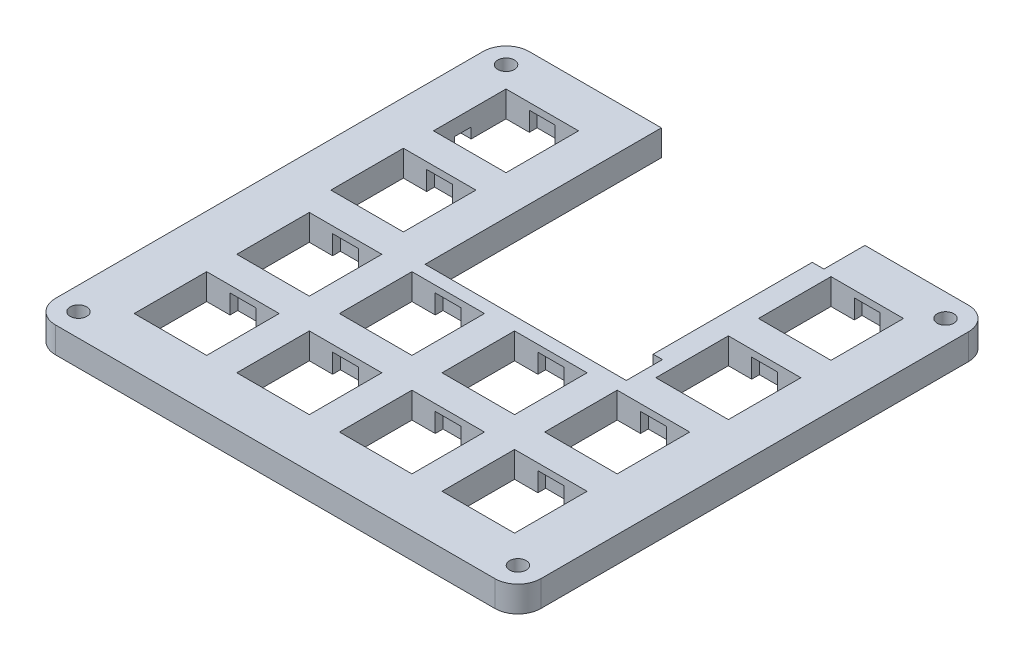
SolidWorks part; units mm, degrees
ref_plane "Front Plane" through (0, 0, 0) normal (0, 0, 1) x (1, 0, 0)
ref_plane "Top Plane" through (0, 0, 0) normal (0, 1, 0) x (1, 0, 0)
ref_plane "Right Plane" through (0, 0, 0) normal (1, 0, 0) x (0, 0, -1)
sketch "Sketch2" plane through (0, 0, 0) normal (0, 1, 0) x (1, 0, 0)
  line L6 (-46.8585, -41.275) -> (-46.8585, 41.275)
  line L8 (46.8585, -41.275) -> (46.8585, 41.275)
  line L9 (42.418, -45.7155) -> (-42.418, -45.7155)
  line L10 (-42.418, 45.7155) -> (-16.8754, 45.7155)
  line L12 (22.418, 41.275) -> (22.418, 39.575)
  line L13 (22.418, 39.575) -> (22.418, 37.7973)
  line L16 (42.418, 27.292) -> (38.3626, 27.292)
  line L18 (42.418, 30.492) -> (38.3626, 30.492)
  line L19 (42.418, 30.492) -> (46.218, 30.492)
  line L20 (46.218, 30.492) -> (46.218, 27.292)
  line L21 (46.218, 27.292) -> (42.418, 27.292)
  line L24 (-46.218, 28.892) -> (-46.218, 30.492)
  line L25 (-46.218, 30.492) -> (-38.3754, 30.492)
  line L26 (-46.218, 28.892) -> (-46.218, 27.292)
  line L27 (-46.218, 27.292) -> (-38.3754, 27.292)
  line L29 (20.1687, 37.7973) -> (20.1687, 9.575)
  line L30 (22.418, 37.7973) -> (20.1687, 37.7973)
  line L31 (20.1687, 9.575) -> (20.1687, 7.075)
  line L32 (20.1687, 7.075) -> (21.9687, 7.075)
  line L33 (-9.9124, 0.0949) -> (21.9687, 0.0949)
  line L35 (21.9687, 7.075) -> (21.9687, 0.0949)
  line L36 (22.418, 41.275) -> (22.418, 45.7155)
  line L38 (-16.8754, 30.2189) -> (-16.8754, 0.0949)
  line L39 (-16.8754, 0.0949) -> (-9.9124, 0.0949)
  line L40 (-16.8754, 30.2189) -> (-16.8754, 45.7155)
  line L41 (-31.3754, 37.2189) -> (-38.3754, 37.2189)
  line L42 (-38.3754, 37.2189) -> (-38.3754, 23.2189)
  line L43 (-38.3754, 23.2189) -> (-24.3754, 23.2189)
  line L44 (-24.3754, 23.2189) -> (-24.3754, 37.2189)
  line L45 (-24.3754, 37.2189) -> (-31.3754, 37.2189)
  line L47 (-38.3754, 10.4069) -> (-38.3754, 17.4069)
  line L48 (-38.3754, 17.4069) -> (-24.3754, 17.4069)
  line L49 (-24.3754, 17.4069) -> (-24.3754, 3.4069)
  line L50 (-24.3754, 3.4069) -> (-38.3754, 3.4069)
  line L51 (-38.3754, 3.4069) -> (-38.3754, 10.4069)
  line L53 (-36.7244, -9.4051) -> (-36.7244, -2.4051)
  line L54 (-36.7244, -2.4051) -> (-22.7244, -2.4051)
  line L55 (-22.7244, -2.4051) -> (-22.7244, -16.4051)
  line L56 (-22.7244, -16.4051) -> (-36.7244, -16.4051)
  line L57 (-36.7244, -16.4051) -> (-36.7244, -9.4051)
  line L59 (-36.7244, -29.2171) -> (-36.7244, -22.2171)
  line L60 (-36.7244, -22.2171) -> (-22.7244, -22.2171)
  line L61 (-22.7244, -22.2171) -> (-22.7244, -36.2171)
  line L62 (-22.7244, -36.2171) -> (-36.7244, -36.2171)
  line L63 (-36.7244, -36.2171) -> (-36.7244, -29.2171)
  line L65 (-9.9124, -22.2171) -> (-2.9124, -22.2171)
  line L66 (-2.9124, -22.2171) -> (-2.9124, -36.2171)
  line L67 (-2.9124, -36.2171) -> (-16.9124, -36.2171)
  line L68 (-16.9124, -36.2171) -> (-16.9124, -22.2171)
  line L69 (-16.9124, -22.2171) -> (-9.9124, -22.2171)
  line L71 (-9.9124, -16.4051) -> (-2.9124, -16.4051)
  line L72 (-2.9124, -16.4051) -> (-2.9124, -2.4051)
  line L73 (-2.9124, -2.4051) -> (-16.9124, -2.4051)
  line L74 (-16.9124, -2.4051) -> (-16.9124, -16.4051)
  line L75 (-16.9124, -16.4051) -> (-9.9124, -16.4051)
  line L77 (9.8996, -2.4051) -> (2.8996, -2.4051)
  line L78 (2.8996, -2.4051) -> (2.8996, -16.4051)
  line L79 (2.8996, -16.4051) -> (16.8996, -16.4051)
  line L80 (16.8996, -16.4051) -> (16.8996, -2.4051)
  line L81 (16.8996, -2.4051) -> (9.8996, -2.4051)
  line L83 (9.8996, -22.2171) -> (2.8996, -22.2171)
  line L84 (2.8996, -22.2171) -> (2.8996, -36.2171)
  line L85 (2.8996, -36.2171) -> (16.8996, -36.2171)
  line L86 (16.8996, -36.2171) -> (16.8996, -22.2171)
  line L87 (16.8996, -22.2171) -> (9.8996, -22.2171)
  line L89 (36.7116, -29.2171) -> (36.7116, -22.2171)
  line L90 (36.7116, -22.2171) -> (22.7116, -22.2171)
  line L91 (22.7116, -22.2171) -> (22.7116, -36.2171)
  line L92 (22.7116, -36.2171) -> (36.7116, -36.2171)
  line L93 (36.7116, -36.2171) -> (36.7116, -29.2171)
  line L95 (29.7116, -2.4051) -> (22.7116, -2.4051)
  line L96 (22.7116, -2.4051) -> (22.7116, -16.4051)
  line L97 (22.7116, -16.4051) -> (36.7116, -16.4051)
  line L98 (36.7116, -16.4051) -> (36.7116, -2.4051)
  line L99 (36.7116, -2.4051) -> (29.7116, -2.4051)
  line L101 (38.3626, 10.4069) -> (38.3626, 17.4069)
  line L102 (38.3626, 17.4069) -> (24.3626, 17.4069)
  line L103 (24.3626, 17.4069) -> (24.3626, 3.4069)
  line L104 (24.3626, 3.4069) -> (38.3626, 3.4069)
  line L105 (38.3626, 3.4069) -> (38.3626, 10.4069)
  line L106 (38.3626, 30.2189) -> (38.3626, 23.2189)
  line L107 (38.3626, 23.2189) -> (24.3626, 23.2189)
  line L108 (24.3626, 23.2189) -> (24.3626, 37.2189)
  line L109 (24.3626, 37.2189) -> (38.3626, 37.2189)
  line L110 (38.3626, 37.2189) -> (38.3626, 30.2189)
  line L111 (22.418, 45.7155) -> (42.418, 45.7155)
  arc A0 (-42.418, 45.7155) -> (-46.8585, 41.275) centre (-42.418, 41.275) ccw
  arc A1 (42.418, 45.7155) -> (46.8585, 41.275) centre (42.418, 41.275) cw
  arc A2 (-46.8585, -41.275) -> (-42.418, -45.7155) centre (-42.418, -41.275) ccw
  arc A3 (46.8585, -41.275) -> (42.418, -45.7155) centre (42.418, -41.275) cw
  circle A4 centre (42.418, 41.275) radius 1.6
  circle A5 centre (-42.418, 41.275) radius 1.6
  circle A6 centre (-42.418, -41.275) radius 1.6
  circle A7 centre (42.418, -41.275) radius 1.6
extrude "Boss-Extrude1" add sketch "Sketch2" along normal blind 5 contours A3 L8 A1 L111 L36 L12 L13 L30 L29 L31 L32 L35 L33 L39 L38 L40 L10 A0 L6 A2 L9 A7 A6 A5 A4 L105 L104 L103 L102 L101 L99 L98 L97 L96 L95 L93 L92 L91 L90 L89 L87 L86 L85 | L42 L25 L24 L26 L27 | L18 L110 L106 L16 L21 L20 L19 region at (-0.7763, 0, 6.0484) region at (42.2903, 0, -28.892) region at (-42.2967, 0, -28.892)
sketch "Sketch3" plane through (0, 0, 0) normal (0, -1, 0) x (1, 0, 0)
  line L0 (42.418, -41.275) -> (42.418, -28.892)
  line L1 (42.418, -28.892) -> (46.218, -28.892)
  line L2 (46.218, -28.892) -> (46.218, -27.292)
  line L3 (46.218, -27.292) -> (38.3626, -27.292)
  line L4 (38.3626, -37.2189) -> (38.3626, -23.2189) construction
  line L5 (46.218, -28.892) -> (46.218, -30.492)
  line L6 (46.218, -30.492) -> (38.3626, -30.492)
  line L7 (38.3626, -30.492) -> (38.3626, -27.292)
  line L8 (-42.418, -41.275) -> (-42.418, -28.892)
  line L9 (-42.418, -28.892) -> (-46.218, -28.892)
  line L10 (-46.218, -28.892) -> (-46.218, -30.492)
  line L11 (-46.218, -28.892) -> (-46.218, -27.292)
  line L12 (-46.218, -27.292) -> (-38.3754, -27.292)
  line L13 (-38.3754, -37.2189) -> (-38.3754, -23.2189) construction
  line L14 (-46.218, -30.492) -> (-38.3754, -30.492)
  line L15 (-38.3754, -30.492) -> (-38.3754, -27.292)
extrude "Cut-Extrude1" cut sketch "Sketch3" against normal blind 2 contours L7 L6 L0 L1 L2 L3 | L6 L5 L1 L0 | L14 L15 L12 L11 L9 L8 | L10 L14 L8 L9 region at (41.6434, 0, -28.6368) region at (44.318, 0, -29.692) region at (-44.318, 0, -29.692) region at (-41.6504, 0, -28.6362)
sketch "Sketch4" plane through (0, 0, 0) normal (0, -1, 0) x (1, 0, 0)
  line L0 (31.3626, -37.2189) -> (31.3626, -38.7189)
  line L1 (24.3626, -37.2189) -> (38.3626, -37.2189) construction
  line L2 (31.3626, -38.7189) -> (28.8626, -38.7189)
  line L3 (28.8626, -38.7189) -> (28.8626, -37.2189)
  line L4 (28.8626, -37.2189) -> (33.8626, -37.2189)
  line L5 (33.8626, -37.2189) -> (33.8626, -38.7189)
  line L6 (33.8626, -38.7189) -> (31.3626, -38.7189)
  line L7 (31.3626, -23.2189) -> (31.3626, -21.7189)
  line L8 (38.3626, -23.2189) -> (24.3626, -23.2189) construction
  line L9 (31.3626, -21.7189) -> (33.8626, -21.7189)
  line L10 (33.8626, -21.7189) -> (33.8626, -23.2189)
  line L11 (33.8626, -23.2189) -> (28.8626, -23.2189)
  line L12 (28.8626, -23.2189) -> (28.8626, -21.7189)
  line L13 (28.8626, -21.7189) -> (31.3626, -21.7189)
  line L14 (31.3626, -17.4069) -> (31.3626, -18.9069)
  line L15 (38.3626, -17.4069) -> (24.3626, -17.4069) construction
  line L16 (31.3626, -18.9069) -> (33.8626, -18.9069)
  line L17 (33.8626, -18.9069) -> (33.8626, -17.4069)
  line L18 (33.8626, -17.4069) -> (28.8626, -17.4069)
  line L19 (28.8626, -17.4069) -> (28.8626, -18.9069)
  line L20 (28.8626, -18.9069) -> (31.3626, -18.9069)
  line L21 (31.3626, -3.4069) -> (31.3626, -1.9069)
  line L22 (24.3626, -3.4069) -> (38.3626, -3.4069) construction
  line L23 (31.3626, -1.9069) -> (33.8626, -1.9069)
  line L24 (33.8626, -1.9069) -> (33.8626, -3.4069)
  line L25 (33.8626, -3.4069) -> (28.8626, -3.4069)
  line L26 (28.8626, -3.4069) -> (28.8626, -1.9069)
  line L27 (28.8626, -1.9069) -> (31.3626, -1.9069)
  line L28 (29.7116, 2.4051) -> (29.7116, 0.9051)
  line L29 (36.7116, 2.4051) -> (22.7116, 2.4051) construction
  line L30 (29.7116, 0.9051) -> (32.2116, 0.9051)
  line L31 (32.2116, 0.9051) -> (32.2116, 2.4051)
  line L32 (32.2116, 2.4051) -> (27.2116, 2.4051)
  line L33 (27.2116, 2.4051) -> (27.2116, 0.9051)
  line L34 (27.2116, 0.9051) -> (29.7116, 0.9051)
  line L35 (29.7116, 16.4051) -> (29.7116, 17.9051)
  line L36 (22.7116, 16.4051) -> (36.7116, 16.4051) construction
  line L37 (29.7116, 17.9051) -> (32.2116, 17.9051)
  line L38 (32.2116, 17.9051) -> (32.2116, 16.4051)
  line L39 (32.2116, 16.4051) -> (27.2116, 16.4051)
  line L40 (27.2116, 16.4051) -> (27.2116, 17.9051)
  line L41 (27.2116, 17.9051) -> (29.7116, 17.9051)
  line L42 (29.7116, 22.2171) -> (29.7116, 20.7171)
  line L43 (36.7116, 22.2171) -> (22.7116, 22.2171) construction
  line L44 (29.7116, 20.7171) -> (32.2116, 20.7171)
  line L45 (32.2116, 20.7171) -> (32.2116, 22.2171)
  line L46 (32.2116, 22.2171) -> (27.2116, 22.2171)
  line L47 (27.2116, 22.2171) -> (27.2116, 20.7171)
  line L48 (27.2116, 20.7171) -> (29.7116, 20.7171)
  line L49 (29.7116, 36.2171) -> (29.7116, 37.7171)
  line L50 (22.7116, 36.2171) -> (36.7116, 36.2171) construction
  line L51 (29.7116, 37.7171) -> (32.2116, 37.7171)
  line L52 (32.2116, 37.7171) -> (32.2116, 36.2171)
  line L53 (32.2116, 36.2171) -> (27.2116, 36.2171)
  line L54 (27.2116, 36.2171) -> (27.2116, 37.7171)
  line L55 (27.2116, 37.7171) -> (29.7116, 37.7171)
  line L56 (9.8996, 2.4051) -> (9.8996, 0.9051)
  line L57 (16.8996, 2.4051) -> (2.8996, 2.4051) construction
  line L58 (9.8996, 0.9051) -> (12.3996, 0.9051)
  line L59 (12.3996, 0.9051) -> (12.3996, 2.4051)
  line L60 (12.3996, 2.4051) -> (7.3996, 2.4051)
  line L61 (7.3996, 2.4051) -> (7.3996, 0.9051)
  line L62 (7.3996, 0.9051) -> (9.8996, 0.9051)
  line L63 (9.8996, 16.4051) -> (9.8996, 17.9051)
  line L64 (2.8996, 16.4051) -> (16.8996, 16.4051) construction
  line L65 (9.8996, 17.9051) -> (7.3996, 17.9051)
  line L66 (7.3996, 17.9051) -> (7.3996, 16.4051)
  line L67 (7.3996, 16.4051) -> (12.3996, 16.4051)
  line L68 (12.3996, 16.4051) -> (12.3996, 17.9051)
  line L69 (12.3996, 17.9051) -> (9.8996, 17.9051)
  line L70 (9.8996, 22.2171) -> (9.8996, 20.7171)
  line L71 (16.8996, 22.2171) -> (2.8996, 22.2171) construction
  line L72 (9.8996, 20.7171) -> (7.3996, 20.7171)
  line L73 (7.3996, 20.7171) -> (7.3996, 22.2171)
  line L74 (7.3996, 22.2171) -> (12.3996, 22.2171)
  line L75 (12.3996, 22.2171) -> (12.3996, 20.7171)
  line L76 (12.3996, 20.7171) -> (9.8996, 20.7171)
  line L77 (9.8996, 36.2171) -> (9.8996, 37.7171)
  line L78 (2.8996, 36.2171) -> (16.8996, 36.2171) construction
  line L79 (9.8996, 37.7171) -> (7.3996, 37.7171)
  line L80 (7.3996, 37.7171) -> (7.3996, 36.2171)
  line L81 (7.3996, 36.2171) -> (12.3996, 36.2171)
  line L82 (12.3996, 36.2171) -> (12.3996, 37.7171)
  line L83 (12.3996, 37.7171) -> (9.8996, 37.7171)
  line L84 (-9.9124, 2.4051) -> (-9.9124, 0.9051)
  line L85 (-2.9124, 2.4051) -> (-16.9124, 2.4051) construction
  line L86 (-9.9124, 0.9051) -> (-12.4124, 0.9051)
  line L87 (-12.4124, 0.9051) -> (-12.4124, 2.4051)
  line L88 (-12.4124, 2.4051) -> (-7.4124, 2.4051)
  line L89 (-7.4124, 2.4051) -> (-7.4124, 0.9051)
  line L90 (-7.4124, 0.9051) -> (-9.9124, 0.9051)
  line L91 (-9.9124, 16.4051) -> (-9.9124, 17.9051)
  line L92 (-16.9124, 16.4051) -> (-2.9124, 16.4051) construction
  line L93 (-9.9124, 17.9051) -> (-12.4124, 17.9051)
  line L94 (-12.4124, 17.9051) -> (-12.4124, 16.4051)
  line L95 (-12.4124, 16.4051) -> (-7.4124, 16.4051)
  line L96 (-7.4124, 16.4051) -> (-7.4124, 17.9051)
  line L97 (-7.4124, 17.9051) -> (-9.9124, 17.9051)
  line L98 (-9.9124, 22.2171) -> (-9.9124, 20.7171)
  line L99 (-16.9124, 22.2171) -> (-2.9124, 22.2171) construction
  line L100 (-9.9124, 20.7171) -> (-7.4124, 20.7171)
  line L101 (-7.4124, 20.7171) -> (-7.4124, 22.2171)
  line L102 (-7.4124, 22.2171) -> (-12.4124, 22.2171)
  line L103 (-12.4124, 22.2171) -> (-12.4124, 20.7171)
  line L104 (-12.4124, 20.7171) -> (-9.9124, 20.7171)
  line L105 (-9.9124, 36.2171) -> (-9.9124, 37.7171)
  line L106 (-2.9124, 36.2171) -> (-16.9124, 36.2171) construction
  line L107 (-9.9124, 37.7171) -> (-7.4124, 37.7171)
  line L108 (-7.4124, 37.7171) -> (-7.4124, 36.2171)
  line L109 (-7.4124, 36.2171) -> (-12.4124, 36.2171)
  line L110 (-12.4124, 36.2171) -> (-12.4124, 37.7171)
  line L111 (-12.4124, 37.7171) -> (-9.9124, 37.7171)
  line L112 (-31.3754, -37.2189) -> (-31.3754, -38.7189)
  line L113 (-24.3754, -37.2189) -> (-38.3754, -37.2189) construction
  line L114 (-31.3754, -38.7189) -> (-33.8754, -38.7189)
  line L115 (-33.8754, -38.7189) -> (-33.8754, -37.2189)
  line L116 (-33.8754, -37.2189) -> (-28.8754, -37.2189)
  line L117 (-28.8754, -37.2189) -> (-28.8754, -38.7189)
  line L118 (-28.8754, -38.7189) -> (-31.3754, -38.7189)
  line L119 (-31.3754, -23.2189) -> (-31.3754, -21.7189)
  line L120 (-38.3754, -23.2189) -> (-24.3754, -23.2189) construction
  line L121 (-31.3754, -21.7189) -> (-33.8754, -21.7189)
  line L122 (-33.8754, -21.7189) -> (-33.8754, -23.2189)
  line L123 (-33.8754, -23.2189) -> (-28.8754, -23.2189)
  line L124 (-28.8754, -23.2189) -> (-28.8754, -21.7189)
  line L125 (-31.3754, -21.7189) -> (-28.8754, -21.7189)
  line L126 (-31.3754, -17.4069) -> (-31.3754, -18.9069)
  line L127 (-38.3754, -17.4069) -> (-24.3754, -17.4069) construction
  line L128 (-31.3754, -18.9069) -> (-28.8754, -18.9069)
  line L129 (-28.8754, -18.9069) -> (-28.8754, -17.4069)
  line L130 (-28.8754, -17.4069) -> (-33.8754, -17.4069)
  line L131 (-33.8754, -17.4069) -> (-33.8754, -18.9069)
  line L132 (-33.8754, -18.9069) -> (-31.3754, -18.9069)
  line L133 (-31.3754, -3.4069) -> (-28.8754, -3.4069)
  line L134 (-24.3754, -3.4069) -> (-38.3754, -3.4069) construction
  line L135 (-28.8754, -3.4069) -> (-28.8754, -1.9069)
  line L136 (-28.8754, -1.9069) -> (-33.8754, -1.9069)
  line L137 (-33.8754, -1.9069) -> (-33.8754, -3.4069)
  line L138 (-33.8754, -3.4069) -> (-31.3754, -3.4069)
  line L139 (-29.7244, 2.4051) -> (-29.7244, 0.9051)
  line L140 (-36.7244, 2.4051) -> (-22.7244, 2.4051) construction
  line L141 (-29.7244, 0.9051) -> (-27.2244, 0.9051)
  line L142 (-27.2244, 0.9051) -> (-27.2244, 2.4051)
  line L143 (-27.2244, 2.4051) -> (-32.2244, 2.4051)
  line L144 (-32.2244, 2.4051) -> (-32.2244, 0.9051)
  line L145 (-32.2244, 0.9051) -> (-29.7244, 0.9051)
  line L146 (-29.7244, 16.4051) -> (-29.7244, 17.9051)
  line L147 (-22.7244, 16.4051) -> (-36.7244, 16.4051) construction
  line L148 (-29.7244, 17.9051) -> (-27.2244, 17.9051)
  line L149 (-27.2244, 17.9051) -> (-27.2244, 16.4051)
  line L150 (-27.2244, 16.4051) -> (-32.2244, 16.4051)
  line L151 (-32.2244, 16.4051) -> (-32.2244, 17.9051)
  line L152 (-32.2244, 17.9051) -> (-29.7244, 17.9051)
  line L153 (-29.7244, 22.2171) -> (-29.7244, 20.7171)
  line L154 (-36.7244, 22.2171) -> (-22.7244, 22.2171) construction
  line L155 (-29.7244, 20.7171) -> (-27.2244, 20.7171)
  line L156 (-27.2244, 20.7171) -> (-27.2244, 22.2171)
  line L157 (-27.2244, 22.2171) -> (-32.2244, 22.2171)
  line L158 (-32.2244, 22.2171) -> (-32.2244, 20.7171)
  line L159 (-32.2244, 20.7171) -> (-29.7244, 20.7171)
  line L160 (-29.7244, 36.2171) -> (-29.7244, 37.7171)
  line L161 (-22.7244, 36.2171) -> (-36.7244, 36.2171) construction
  line L162 (-29.7244, 37.7171) -> (-27.2244, 37.7171)
  line L163 (-27.2244, 37.7171) -> (-27.2244, 36.2171)
  line L164 (-27.2244, 36.2171) -> (-32.2244, 36.2171)
  line L165 (-32.2244, 36.2171) -> (-32.2244, 37.7171)
  line L166 (-32.2244, 37.7171) -> (-29.7244, 37.7171)
extrude "Cut-Extrude2" cut sketch "Sketch4" against normal blind 3.7 contours L6 L5 L4 L0 | L4 L3 L2 L0 | L11 L10 L9 L7 | L13 L12 L11 L7 | L25 L24 L23 L21 | L19 L20 L14 L18 | L17 L18 L14 L16 | L27 L26 L25 L21 | L31 L32 L28 L30 | L33 L34 L28 L32 | L39 L38 L37 L35 | L41 L40 L39 L35 | L45 L46 L42 L44 | L47 L48 L42 L46 | L53 L52 L51 L49 | L55 L54 L53 L49 | L82 L83 L77 L81 | L80 L81 L77 L79 | L74 L73 L72 L70 | L76 L75 L74 L70 | L68 L69 L63 L67 | L66 L67 L63 L65 | L59 L60 L56 L58 | L61 L62 L56 L60 | L90 L89 L88 L84 | L88 L87 L86 L84 | L96 L97 L91 L95 | L94 L95 L91 L93 | L101 L102 L98 L100 | L103 L104 L98 L102 | L109 L108 L107 L105 | L111 L110 L109 L105 | L150 L149 L148 L146 | L152 L151 L150 L146 | L158 L159 L153 L157 | L156 L157 L153 L155 | L164 L163 L162 L160 | L166 L165 L164 L160 | L142 L143 L139 L141 | L144 L145 L139 L143 | L137 L138 L133 L135 L136 | L131 L132 L126 L130 | L129 L130 L126 L128 | L122 L123 L119 L121 | L125 L119 L123 L124 | L118 L117 L116 L112 | L116 L115 L114 L112 region at (32.6126, 0, -37.9689) region at (30.1126, 0, -37.9689) region at (30.1126, 0, -22.4689) region at (32.6126, 0, -22.4689) region at (32.6126, 0, -18.1569) region at (30.1126, 0, -18.1569) region at (30.1126, 0, -2.6569) region at (32.6126, 0, -2.6569) region at (30.9616, 0, 1.6551) region at (28.4616, 0, 1.6551) region at (28.4616, 0, 17.1551) region at (30.9616, 0, 17.1551) region at (30.9616, 0, 21.4671) region at (28.4616, 0, 21.4671) region at (28.4616, 0, 36.9671) region at (30.9616, 0, 36.9671) region at (11.1496, 0, 1.6551) region at (8.6496, 0, 1.6551) region at (8.6496, 0, 17.1551) region at (11.1496, 0, 17.1551) region at (11.1496, 0, 21.4671) region at (8.6496, 0, 21.4671) region at (8.6496, 0, 36.9671) region at (11.1496, 0, 36.9671) region at (-8.6624, 0, 1.6551) region at (-11.1624, 0, 1.6551) region at (-11.1624, 0, 17.1551) region at (-8.6624, 0, 17.1551) region at (-8.6624, 0, 21.4671) region at (-11.1624, 0, 21.4671) region at (-11.1624, 0, 36.9671) region at (-8.6624, 0, 36.9671) region at (-30.1254, 0, -37.9689) region at (-32.6254, 0, -37.9689) region at (-32.6254, 0, -22.4689) region at (-30.1254, 0, -22.4689) region at (-30.1254, 0, -18.1569) region at (-32.6254, 0, -18.1569) region at (-31.3754, 0, -2.6569) region at (-28.4744, 0, 1.6551) region at (-30.9744, 0, 1.6551) region at (-30.9744, 0, 17.1551) region at (-28.4744, 0, 17.1551) region at (-28.4744, 0, 21.4671) region at (-30.9744, 0, 21.4671) region at (-30.9744, 0, 36.9671) region at (-28.4744, 0, 36.9671)
